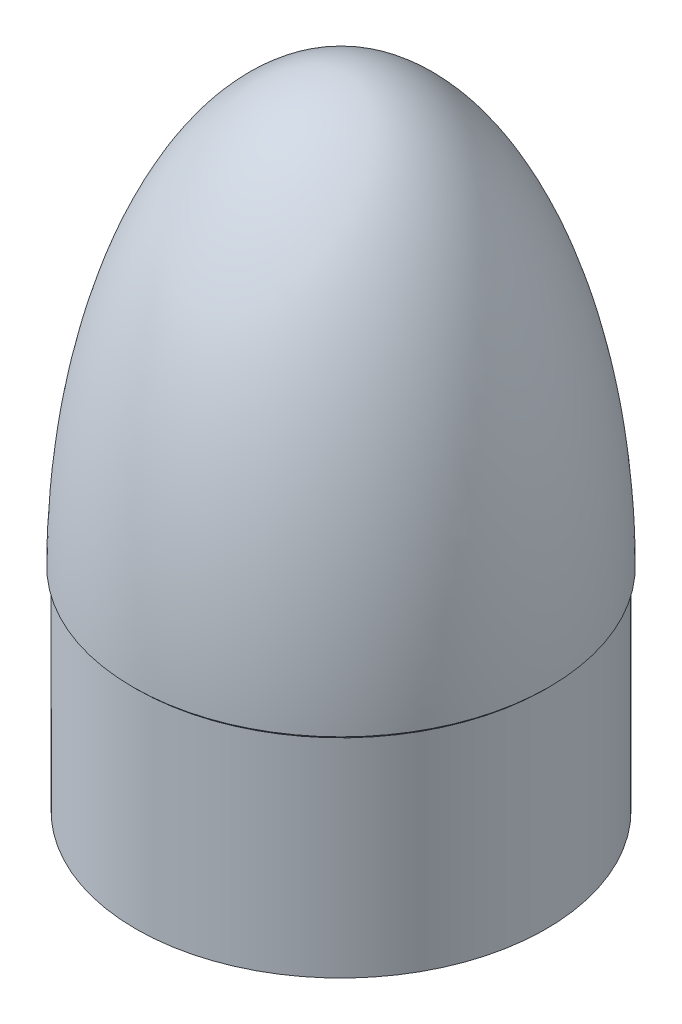
SolidWorks part; units mm, degrees
ref_plane "Front Plane" through (0, 0, 0) normal (0, 0, 1) x (1, 0, 0)
ref_plane "Top Plane" through (0, 0, 0) normal (0, 1, 0) x (1, 0, 0)
ref_plane "Right Plane" through (0, 0, 0) normal (1, 0, 0) x (0, 0, -1)
sketch "Sketch1" plane through (0, 0, 0) normal (0, 0, 1) x (1, 0, 0)
  line L3 (0, 0) -> (0, 202.3003) construction
  line L5 (0, 165.1) -> (0, 162.1028)
  line L10 (76.3778, 0) -> (76.3778, -81.661)
  line L12 (76.3778, -81.661) -> (79.375, -81.661)
  line L13 (79.375, -81.661) -> (79.375, -1.143)
  line L14 (80.518, 0) -> (79.375, -1.143)
  line L15 (79.375, -1.143) -> (80.518, -1.143) construction
  ellipse E0 centre (0, 0) end of major axis (0, 162.1028) minor radius 76.3778 (76.3778, 0) -> (0, 162.1028) ccw
  ellipse E1 centre (0, 0) end of major axis (0, -165.1) minor radius 80.518 (80.518, 0) -> (0, 165.1) ccw
  dimension "D1" = 158.75
  dimension "D2" = 80.518
  dimension "D3" = 165.1
  dimension "D4" = 161.036
  dimension "D5" = 2.9972
  dimension "D6" = 2.9972
  dimension "D7" = 45
revolve "Revolve1" add sketch "Sketch1" angle 360 about L5
